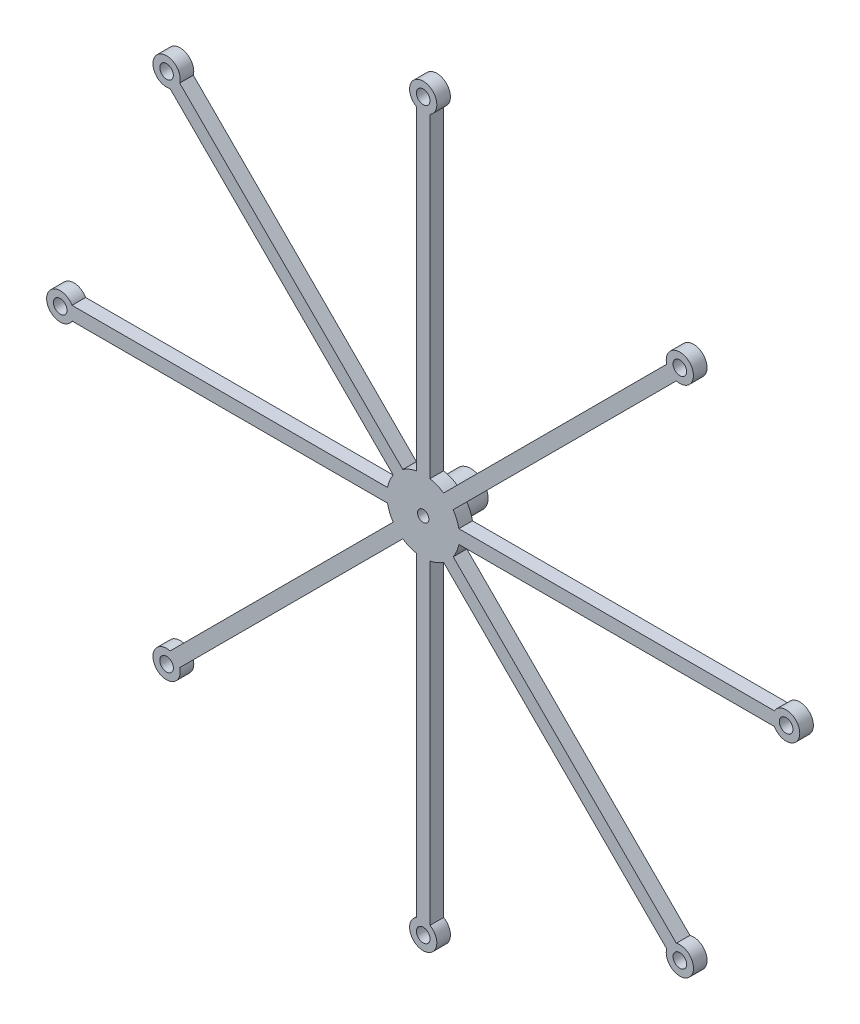
SolidWorks part; units mm, degrees
ref_plane "前视基准面" through (0, 0, 0) normal (0, 0, 1) x (1, 0, 0)
ref_plane "上视基准面" through (0, 0, 0) normal (0, 1, 0) x (1, 0, 0)
ref_plane "右视基准面" through (0, 0, 0) normal (1, 0, 0) x (0, 0, -1)
other "Configuration Table"
ref_axis "基准轴1" through (0, 0, 0) along (0, 0, 1)
sketch "草图1" plane through (0, 0, 0) normal (0, 0, 1) x (1, 0, 0)
  circle A0 centre (0, 0) radius 8
  dimension "D1" = 16
extrude "凸台-拉伸1" add sketch "草图1" along normal blind 3
sketch "草图2" plane through (0, 0, 3) normal (0, 0, 1) x (1, 0, 0)
  line L0 (0, 0) -> (80, 0) construction
  line L1 (77.4019, 1.5) -> (7.8581, 1.5)
  line L2 (7.8581, -1.5) -> (77.4019, -1.5)
  circle A0 centre (80, 0) radius 1.5
  circle A1 centre (80, 0) radius 3
  circle A2 centre (0, 0) radius 8 construction
  circle M6 centre (0, 0) radius 8
  dimension "D2" = 6
  dimension "D3" = 3
  dimension "D1" = 3
  dimension "D4" = 80
extrude "凸台-拉伸-辐条" add sketch "草图2" against normal up to surface (3 mm away) contours L0 A1 L1 M6 | L0 L2 A1 M6 | A1 A0 region at (42.5416, 0.751, 3) region at (42.5416, -0.751, 3) region at (77.1842, 0.7545, 3) up to face at (8, 0, 0)
pattern_circular "阵列(圆周)3" count 8 over 360 about axis through (0, 0, 0) along (0, 0, 1) of "凸台-拉伸-辐条"
sketch "草图3" plane through (0, 0, 0) normal (0, 0, -1) x (-1, 0, 0)
  circle A0 centre (0, 0) radius 3.8
  dimension "D1" = 7.6
extrude "凸台-拉伸3" add sketch "草图3" along normal blind 7.5
sketch "草图4" plane through (0, 0, -7.5) normal (0, 0, -1) x (-1, 0, 0)
  circle A0 centre (0, 0) radius 1.25
  dimension "D1" = 2.5
extrude "切除-拉伸1" cut sketch "草图4" against normal through all
